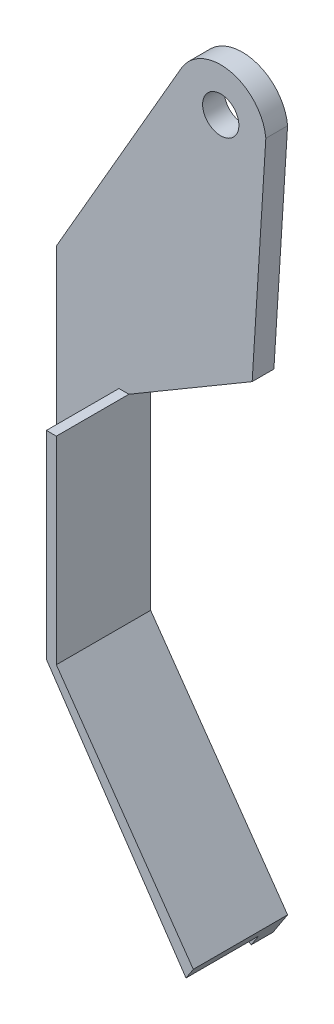
SolidWorks part; units mm, degrees
ref_plane "前视基准面" through (0, 0, 0) normal (0, 0, 1) x (1, 0, 0)
ref_plane "上视基准面" through (0, 0, 0) normal (0, 1, 0) x (1, 0, 0)
ref_plane "右视基准面" through (0, 0, 0) normal (1, 0, 0) x (0, 0, -1)
sketch "草图1" plane through (0, 0, 0) normal (0, 0, 1) x (1, 0, 0)
  line L0 (0.4413, 66.8945) -> (-16.8792, 36.8945)
  line L1 (-16.8792, 36.8945) -> (-16.8792, -3.1055)
  line L2 (-16.8792, -3.1055) -> (-5.3322, -23.1055)
  line L5 (-7.0008, 37.5151) -> (-6.8792, 37.579)
  line L26 (-5.3322, -23.1055) -> (9.9927, -33.1055)
  line L27 (11.9998, 64.1907) -> (10.1143, 34.1907)
  line L28 (10.1143, 34.1907) -> (-6.8792, 24.1907)
  line L29 (-6.8792, 24.1907) -> (-6.8792, 14.1907)
  line L32 (-6.8792, 14.1907) -> (-6.8792, -3.1055)
  line L35 (-6.8792, -3.1055) -> (11.9998, -30.0298)
  line L36 (11.9998, -30.0298) -> (9.9927, -33.1055)
  arc A4 (0.4413, 66.8945) -> (11.9998, 64.1907) centre (5.7669, 63.6033) cw
  dimension "D7" = 30
  dimension "D8" = 10
  dimension "D9" = 10
  dimension "D6" = 10
  dimension "D1" = 150
  dimension "D2" = 150
  dimension "D3" = 30
  dimension "D4" = 40
  dimension "D5" = 20
  dimension "D10" = 10
sketch "草图2" plane through (0, 0, 0) normal (0, 0, 1) x (1, 0, 0)
  circle A2 centre (5.7844, 63.8812) radius 2.5
  dimension "D1" = 5
extrude "凸台-拉伸4" add sketch "草图1" along normal blind 3 contours A4 L0 L1 L2 L26 L36 L35 L32 L29 L28 L27 region at (6.9493, 68.6579, 0)
extrude "切除-拉伸1" cut sketch "草图2" along normal through all
sketch "草图6" plane through (0, 0, 0) normal (0, 0, -1) x (-1, 0, 0)
  line L0 (6.8792, 24.1907) -> (8.2484, 24.1907)
  line L1 (8.2484, 24.1907) -> (8.2484, -3.1455)
  line L2 (8.2484, -3.1455) -> (-10.9962, -31.5677)
  line L3 (-11.9998, -30.0298) -> (-9.9927, -33.1055) construction
  line L13 (-11.9998, 64.1907) -> (-10.1143, 34.1907)
  line L14 (-10.1143, 34.1907) -> (6.8792, 24.1907)
  line L15 (6.8792, 24.1907) -> (6.8792, -3.1055)
  line L16 (6.8792, -3.1055) -> (-11.9998, -30.0298)
  line L17 (-11.9998, -30.0298) -> (-9.9927, -33.1055)
  line L18 (-9.9927, -33.1055) -> (5.3322, -23.1055)
  line L19 (5.3322, -23.1055) -> (16.8792, -3.1055)
  line L20 (16.8792, -3.1055) -> (16.8792, 36.8945)
  line L21 (16.8792, 36.8945) -> (-0.4413, 66.8945)
  line L24 (6.8792, 24.1907) -> (6.8792, -3.1055)
  line L25 (6.8792, -3.1055) -> (-11.9998, -30.0298)
  line L26 (-11.9998, -30.0298) -> (-10.9962, -31.5677)
  arc A1 (-0.4413, 66.8945) -> (-11.9998, 64.1907) centre (-5.7669, 63.6033) ccw
  dimension "D1" = 0
extrude "凸台-拉伸6" add sketch "草图6" against normal blind 13
equation "\"13mm.\"=10"
